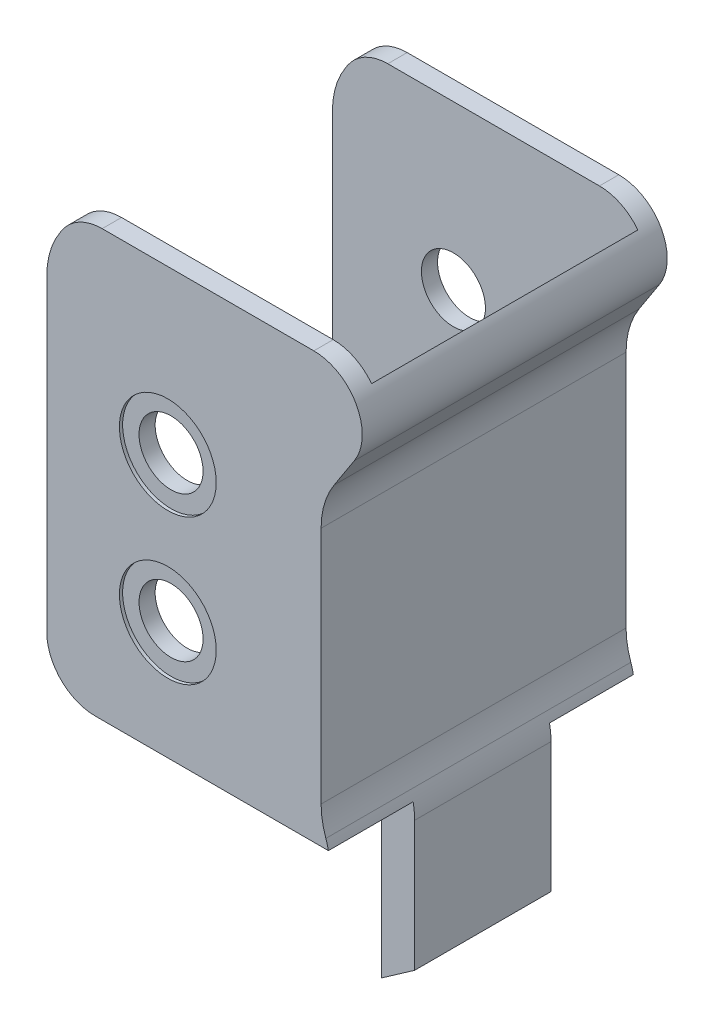
SolidWorks part; units mm, degrees
ref_plane "Front Plane" through (0, 0, 0) normal (0, 0, 1) x (1, 0, 0)
ref_plane "Top Plane" through (0, 0, 0) normal (0, 1, 0) x (1, 0, 0)
ref_plane "Right Plane" through (0, 0, 0) normal (1, 0, 0) x (0, 0, -1)
sketch "Sketch1" plane through (0, 0, 0) normal (0, 0, 1) x (1, 0, 0)
  line L0 (17, 26.68) -> (17, 41.4833)
  line L1 (17.8066, 44.2065) -> (22.0746, 50.7786)
  line L3 (22.0746, 50.7786) -> (1.8045, 50.7786)
  line L4 (0.8066, 49.2421) -> (14.4977, 70.3245) construction
  line L5 (1.8045, 50.7786) -> (0.8066, 49.2421)
  line L6 (0, 46.5189) -> (0, 24.4055)
  line L7 (0, 46.5189) -> (0, 15) construction
  line L8 (17.5473, 24.4055) -> (0, 24.4055)
  line L10 (20.7496, 52.4105) -> (15.8066, 44.7989) construction
  line L11 (15, 42.0757) -> (15, 26.5504) construction
  line L12 (0, 26.68) -> (17, 26.68) construction
  arc A0 (17, 41.4833) -> (17.8066, 44.2065) centre (22, 41.4833) cw
  arc A1 (0.8066, 49.2421) -> (0, 46.5189) centre (5, 46.5189) ccw
  arc A2 (17, 26.68) -> (17.5473, 24.4055) centre (22, 26.68) ccw
  arc A3 (15, 26.5504) -> (15.4834, 24.4055) centre (20, 26.5504) ccw construction
  dimension "D1" = 2
  dimension "D2" = 2
  dimension "D3" = 5
extrude "Boss-Extrude1" add sketch "Sketch1" against normal blind 20.5 from offset 2
ref_plane "Plane1" through (0, 0, -8.25) normal (0, 0, 1) x (1, 0, 0)
sketch "Sketch2" plane through (0, 0, -8.25) normal (0, 0, 1) x (1, 0, 0)
  line L0 (1.8045, 50.7786) -> (0.8066, 49.2421)
  line L1 (0, 46.5189) -> (0, 24.4055)
  line L2 (0, 24.4055) -> (17.5473, 24.4055) construction
  line L4 (15, 26.5504) -> (15, 42.0757)
  line L5 (15.8066, 44.7989) -> (19.6899, 50.7786)
  line L6 (22.0746, 50.7786) -> (1.8045, 50.7786) construction
  line L7 (20.7496, 52.4105) -> (15.8066, 44.7989) construction
  line L8 (19.6899, 50.7786) -> (1.8045, 50.7786)
  line L10 (17, 26.68) -> (17, 41.4833) construction
  line L12 (15.4834, 24.4055) -> (19.9501, 15) construction
  line L13 (0, 24.4055) -> (15.4834, 24.4055)
  arc A0 (0.8066, 49.2421) -> (0, 46.5189) centre (5, 46.5189) ccw
  arc A1 (15, 42.0757) -> (15.8066, 44.7989) centre (20, 42.0757) cw
  arc A2 (17.8066, 44.2065) -> (17, 41.4833) centre (22, 41.4833) ccw construction
  arc A3 (15, 26.5504) -> (15.4834, 24.4055) centre (20, 26.5504) ccw
  arc A4 (17, 26.68) -> (17.5473, 24.4055) centre (22, 26.68) ccw construction
  dimension "D1" = 2
extrude "Cut-Extrude1" cut sketch "Sketch2" against normal mid plane 16.5
sketch "Sketch4" plane through (0, 0, 2) normal (0, 0, 1) x (1, 0, 0)
  line L4 (0, 46.5189) -> (0, 24.4055) construction
  circle A0 centre (7.5, 40.68) radius 1.9844
  circle A1 centre (7.5, 31.68) radius 1.9844
  dimension "D1" = 3.9688
  dimension "D2" = 9
  dimension "D3" = 5
  dimension "D4" = 7.5
extrude "Cut-Extrude2" cut sketch "Sketch4" against normal through all
sketch "Sketch5" plane through (0, 0, 2) normal (0, 0, 1) x (1, 0, 0)
  circle A0 centre (7.5, 40.68) radius 3
  circle A2 centre (7.5, 31.68) radius 3
  dimension "D1" = 6
extrude "Cut-Extrude3" cut sketch "Sketch5" against normal blind 1
sketch "Sketch6" plane through (0, 0, -18.5) normal (0, 0, -1) x (-1, 0, 0)
  circle A0 centre (-7.5, 40.68) radius 3.4443
  circle A1 centre (-7.5, 31.68) radius 3.4443
  dimension "D1" = 6.8887
extrude "Cut-Extrude4" cut sketch "Sketch6" against normal blind 1
fillet "Fillet1" radius 3 1 edges at (22.0746, 50.7786, -8.25)
ref_plane "Plane2" through (0, 26.68, 0) normal (0, 1, 0) x (0, 0, 1)
sketch "Sketch7" plane through (0, 26.68, 0) normal (0, 1, 0) x (0, 0, 1)
  line L0 (-18.5, 17) -> (2, 17) construction
  line L1 (-4.35, 17) -> (-12.2, 17)
  line L2 (-4.35, 17) -> (-4.35, 15.4834)
  line L3 (-4.35, 15.4834) -> (-12.2, 15.4834)
  line L4 (-12.2, 17) -> (-12.2, 15.4834)
  line L5 (-16.5, 15.4834) -> (0, 15.4834) construction
  line L7 (-12.7, 18.1217) -> (-12.7, 17.0295) construction
  line L9 (-3.85, 2) -> (-3.85, 14) construction
  dimension "D1" = 0.5
  dimension "D2" = 0.5
extrude "Boss-Extrude2" [suppressed] add sketch "Sketch7" against normal blind 10.37
sketch "Sketch8" [suppressed] plane through (0, 0, -4.35) normal (0, 0, 1) x (1, 0, 0)
  line L0 (15.4834, 16.31) -> (15.4834, 15.31)
  line L1 (15.4834, 15.31) -> (17, 16.31)
  line L2 (17, 16.31) -> (15.4834, 16.31)
  dimension "D1" = 1
extrude "Boss-Extrude3" [suppressed] add sketch "Sketch8" against normal up to surface (7.85 mm away)
sketch "Sketch9" plane through (0, 24.4055, 0) normal (0, -1, 0) x (-1, 0, 0)
  line L0 (-17.5473, 18.5) -> (-17.5473, -2) construction
  line L1 (-17.5473, 4.05) -> (-15.4834, 4.05)
  line L2 (-17.5473, 4.05) -> (-17.5473, 12.5)
  line L3 (-17.5473, 12.5) -> (-15.4834, 12.5)
  line L4 (-15.4834, 4.05) -> (-15.4834, 12.5)
  line L5 (-15.4834, 16.5) -> (-15.4834, 0) construction
  line L7 (-17.0295, 12.7) -> (-2, 12.7) construction
  line L8 (-2, 3.85) -> (-14, 3.85) construction
  dimension "D1" = 0.2
  dimension "D2" = 0.2
extrude "Boss-Extrude4" add sketch "Sketch9" along normal blind 9
sketch "Sketch10" plane through (0, 0, -4.05) normal (0, 0, 1) x (1, 0, 0)
  line L0 (15.4834, 15.4055) -> (15.4834, 13.9614)
  line L1 (15.4834, 13.9614) -> (17.5473, 15.4055)
  line L2 (17.5473, 15.4055) -> (15.4834, 15.4055)
  dimension "D1" = 34.98
extrude "Boss-Extrude5" add sketch "Sketch10" against normal up to surface (8.45 mm away) up to face at (16.5154, 19.9055, -12.5)
sketch "Sketch11" plane through (0, 0, 2) normal (0, 0, 1) x (1, 0, 0)
  line L0 (17.2645, 25.0752) -> (17.5473, 25.0752)
  line L1 (17.5473, 25.0752) -> (17.5473, 23.4567)
  line L2 (17.5473, 15.4055) -> (17.5473, 24.4055) construction
  arc A0 (17.5473, 23.4567) -> (17.2645, 25.0752) centre (12.7738, 23.4567) ccw
  arc A1 (17, 26.68) -> (17.5473, 24.4055) centre (22, 26.68) ccw construction
extrude "Cut-Extrude5" cut sketch "Sketch11" against normal through all
fillet "Fillet3" radius 3 4 edges at (0, 24.4055, -17.5) (0, 24.4055, 1) (1.8045, 50.7786, -17.5) (1.8045, 50.7786, 1)
sketch "Sketch12" plane through (0, 0, 0) normal (-1, 0, 0) x (0, 0, 1)
  line L0 (-18.5, 46.5189) -> (-18.5, 27.4055) construction
  line L1 (-22.1175, 50.7786) -> (-17.7, 50.7786)
  line L2 (-22.1175, 50.7786) -> (-22.1175, 13.9614)
  line L3 (-22.1175, 13.9614) -> (-17.7, 13.9614)
  line L4 (-17.7, 50.7786) -> (-17.7, 13.9614)
  line L5 (-12.5, 13.9614) -> (-4.05, 13.9614) construction
  line L6 (-18.5, 50.7786) -> (-16.5, 50.7786) construction
  line L7 (-8.25, 62.3336) -> (-8.25, 7.6275) construction
  line L8 (-8.25, -10.7521) -> (-8.25, 10.7521) construction
  line L9 (1.2, 50.7786) -> (1.2, 13.9614)
  line L10 (5.6175, 13.9614) -> (1.2, 13.9614)
  line L11 (5.6175, 50.7786) -> (5.6175, 13.9614)
  line L12 (5.6175, 50.7786) -> (1.2, 50.7786)
  dimension "D1" = 0.8
extrude "Cut-Extrude6" cut sketch "Sketch12" against normal through all
